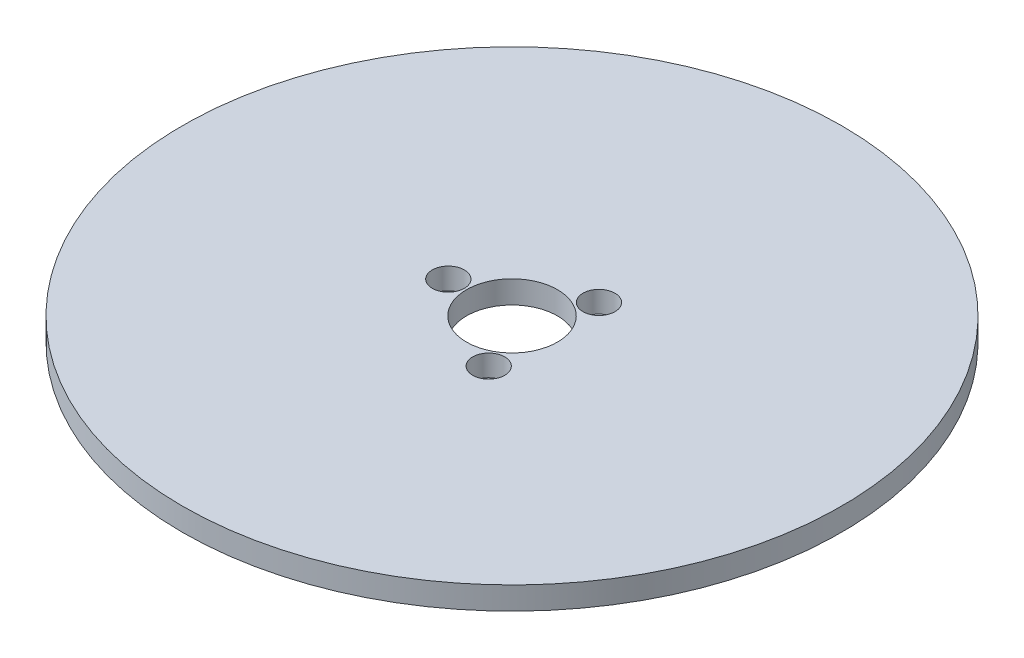
SolidWorks part; units mm, degrees
ref_plane "Front Plane" through (0, 0, 0) normal (0, 0, 1) x (1, 0, 0)
ref_plane "Top Plane" through (0, 0, 0) normal (0, 1, 0) x (1, 0, 0)
ref_plane "Right Plane" through (0, 0, 0) normal (1, 0, 0) x (0, 0, -1)
sketch "Sketch1" plane through (0, 0, 0) normal (0, 1, 0) x (1, 0, 0)
  circle A0 centre (0, 0) radius 72.5
  dimension "FLANGE_OD" = 145
extrude "Boss-Extrude1" add sketch "Sketch1" along normal blind 5
sketch "Sketch2" plane through (0, 0, 0) normal (0, 1, 0) x (1, 0, 0)
  circle A0 centre (0, 0) radius 10
  dimension "BORE_D" = 20
extrude "Cut-Extrude1" cut sketch "Sketch2" along normal through all
sketch "Sketch3" plane through (0, 5, 0) normal (0, 1, 0) x (1, 0, 0)
  circle A0 centre (0, 0) radius 14.0052 construction
  circle A1 centre (-14.0052, 0) radius 3.525
  dimension "BOLT_D" = 7.05
  dimension "BOLT_PCD" = 28.0105
extrude "Cut-Extrude2" cut sketch "Sketch3" against normal blind 4.708
pattern_circular "CirPattern1" count 3 over 360 about axis through (0, 0, 0) along (0, 1, 0) of "Cut-Extrude2"
